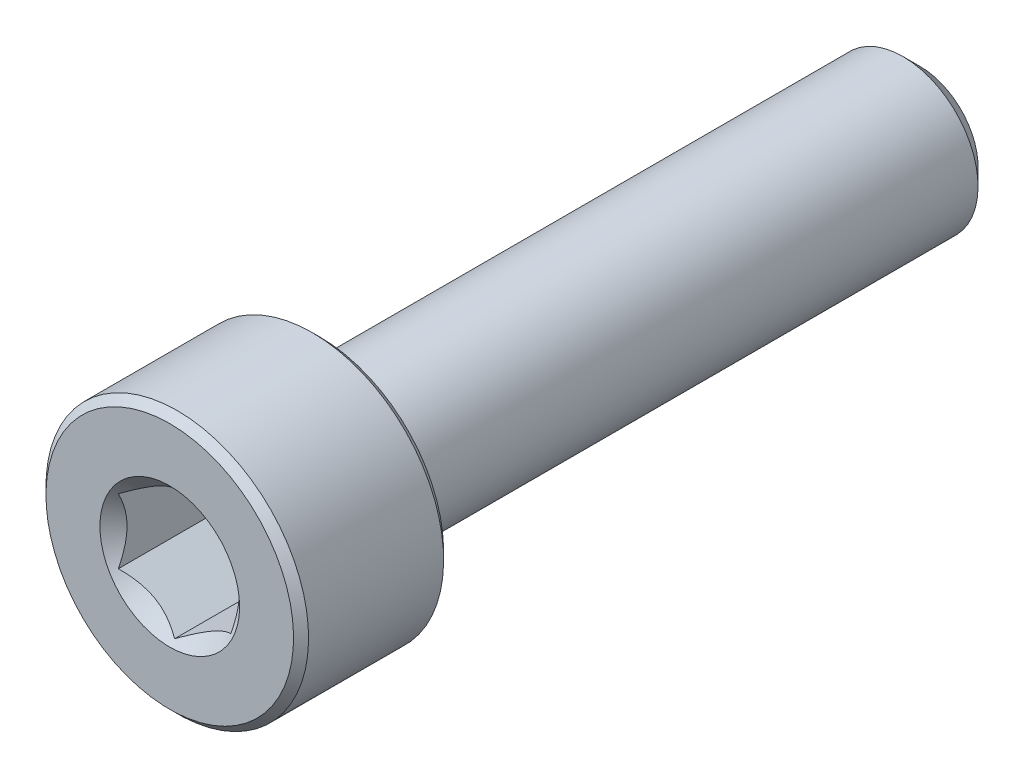
SolidWorks part; units mm, degrees
material "Alloy Steel"
ref_plane "Front Plane" through (0, 0, 0) normal (0, 0, 1) x (1, 0, 0)
ref_plane "Top Plane" through (0, 0, 0) normal (0, 1, 0) x (1, 0, 0)
ref_plane "Right Plane" through (0, 0, 0) normal (1, 0, 0) x (0, 0, -1)
sketch "Sketch1" plane through (0, 0, 0) normal (1, 0, 0) x (0, 0, -1)
  line L0 (-10, 0) -> (10, 0) construction
  line L1 (10, 0) -> (10, 1.5453) construction
  line L2 (10, 1.5453) -> (9.5453, 2) construction
  line L3 (9.5453, 2) -> (9.475, 2) construction
  line L4 (9.475, 2) -> (-6, 2) construction
  line L5 (-6, 2) -> (-6, 3.5) construction
  line L6 (-6, 3.5) -> (-10, 3.5) construction
  line L7 (-10, 3.5) -> (-10, 0) construction
  line L8 (10, 1.5453) -> (10, 2) construction
  line L9 (9.9563, 2.0758) -> (10.3062, 1.4696) construction
  line L10 (10.3062, 1.4696) -> (10.6562, 2.0758) construction
  line L11 (10.6562, 2.0758) -> (9.9563, 2.0758) construction
  line L12 (10.3062, 2.0758) -> (10.3062, 2) construction
  line L13 (10.3062, 1.4696) -> (10.3062, 1.5453) construction
  line L14 (10.2625, 1.5453) -> (10.35, 1.5453) construction
  line L15 (10, 2) -> (10.6125, 2) construction
  line L16 (9.9781, 2.0379) -> (10.6344, 2.0379) construction
  line L17 (10, 0) -> (10, -2) construction
  line L18 (-6.2, 3.5) -> (-6, 3.3) construction
  line L19 (-9.8, 3.5) -> (-10, 3.3) construction
  line L20 (-6, 2) -> (-6, 0) construction
  line L21 (-6, 1) -> (-0.6667, 1) construction
  line L22 (-0.6667, 1) -> (4.6667, 1) construction
  line L23 (4.6667, 1) -> (10, 1) construction
  line L24 (-0.6667, 1) -> (-0.6667, 2) construction
  line L25 (-0.6667, 2) -> (-0.6667, 3.5) construction
  line L26 (4.6667, 1) -> (4.6667, 3.5) construction
  point P0 (-10, 1.5)
  point P3 (8.25, 2)
  point P4 (0, 0)
  point P18 (4.6667, 2)
  point P22 (10.3062, 1.5453)
  point P24 (9.475, 2)
  point P25 (10.3062, 2)
  point P28 (10.3063, 2.0379)
  point P29 (8.25, -2)
  point P30 (-0.6667, 2)
  point P31 (-8, 3.5)
  point P37 (-6.7, 3.5)
  point P38 (-9.7, 3.5)
  point P45 (-0.6667, 1)
  point P46 (4.6667, 1)
  dimension "D2" = 0.0875
  dimension "D7" = 0.2
  dimension "D8" = 0.2
  dimension "D9" = 0.2
  dimension "D10" = 0.1
  dimension "D11" = 0.5
  dimension "Drive Size" = 3
  dimension "Head Diameter" = 7
  dimension "Head Height" = 4
  dimension "Thread Pitch" = 0.7
  dimension "Thread Dia" = 4
  dimension "Length" = 16
  dimension "D12" = 0.525
  dimension "D4" = 1.75
  dimension "D3" = 45
sketch "Sketch2" plane through (0, 0, 0) normal (1, 0, 0) x (0, 0, -1)
  line L0 (-10, 0) -> (-10, 3.3)
  line L1 (-9.8, 3.5) -> (-6.2, 3.5)
  line L2 (-6, 3.3) -> (-6, 2.2)
  line L4 (9.5453, 2) -> (10, 1.5453)
  line L5 (10, 1.5453) -> (10, 0)
  line L6 (-6, 3.5) -> (-10, 3.5) construction
  line L7 (10, 0) -> (-10, 0)
  line L8 (-9.8, 3.5) -> (-10, 3.3) construction
  line L10 (-9.8, 3.5) -> (-10, 3.3)
  line L14 (-6.2, 3.5) -> (-6, 3.3) construction
  line L16 (-6.2, 3.5) -> (-6, 3.3)
  line L17 (-6, 2) -> (-6, 3.5) construction
  line L19 (-5.8, 2) -> (9.5453, 2)
  line L20 (9.475, 2) -> (-6, 2) construction
  arc A1 (-6, 2.2) -> (-5.8, 2) centre (-5.8, 2.2) ccw
  dimension "D3" = 0.2
revolve "Revolve1" add sketch "Sketch2" angle 360 about L7
sketch "Sketch3" plane through (0, 0, 10) normal (0, 0, 1) x (1, 0, 0)
  line L1 (1.5, -0.866) -> (1.5, 0.866)
  line L2 (1.5, 0.866) -> (0, 1.7321)
  line L3 (0, 1.7321) -> (-1.5, 0.866)
  line L4 (-1.5, 0.866) -> (-1.5, -0.866)
  line L5 (-1.5, -0.866) -> (0, -1.7321)
  line L6 (0, -1.7321) -> (1.5, -0.866)
  circle A0 centre (0, 0) radius 1.5 construction
  circle A1 centre (0, 0) radius 3.5 construction
  circle A2 centre (0, 0) radius 3.5 construction
  circle A3 centre (0, 0) radius 1.7321 construction
  point P13 (0, 0)
  dimension "D1" = 3.4641
extrude "Cut-Extrude1" cut sketch "Sketch3" against normal offset from surface (3 mm away) 1 up to face at (0, 3.3, 6)
sketch "Sketch4" plane through (0, 0, 10) normal (0, 0, 1) x (1, 0, 0)
  circle A0 centre (0, 0) radius 1.862
  dimension "D1" = 3.7239
extrude "Cut-Extrude2" cut sketch "Sketch4" against normal up to vertex (2 mm away) draft 45 up to point (0, 3.5, 8)
sketch "Sketch11" plane through (0, 0, 0) normal (1, 0, 0) x (0, 0, -1)
  line L0 (-10, 0) -> (10, 0) construction
  line L1 (-10, 0) -> (10, 0) construction
  line L2 (-3, 0) -> (-3, 2) construction
  line L3 (9.475, 2) -> (-6, 2) construction
  line L4 (7, 0) -> (7, 2) construction
  line L6 (10, 1.5453) -> (10, 2) construction
  point P2 (-3, 0)
  point P3 (7, 0)
  dimension "D2" = 3
sketch "Sketch6" [suppressed] plane through (0, 0, -10) normal (0, 0, -1) x (-1, 0, 0)
  circle A0 centre (0, 0) radius 2
curve "Helix/Spiral1" [suppressed] pitch 0.7 height 16.7 turns 23.8571
sketch "Sketch10" [suppressed] plane through (0, 0, 0) normal (1, 0, 0) x (0, 0, -1)
  line L0 (-5.8, -3.5) -> (-5.8, 3.5)
  line L5 (-10, 0) -> (10, 0) construction
  line L6 (-5.8, 2) -> (-5.8, -2) construction
  point P3 (-5.8, 0)
split "Split1" [suppressed] bodies to split 106
sketch "Sketch7" [suppressed] plane through (0, 0, 0) normal (1, 0, 0) x (0, 0, -1)
  line L0 (9.9781, 2.0379) -> (10.6344, 2.0379)
  line L1 (10.6344, 2.0379) -> (10.35, 1.5453)
  line L2 (10.35, 1.5453) -> (10.2625, 1.5453)
  line L3 (10.2625, 1.5453) -> (9.9781, 2.0379)
sweep "Cut-Sweep1" [suppressed] cut profiles "Sketch7" path "Helix/Spiral1"
sketch "Sketch8" [suppressed] plane through (0, 0, 0) normal (1, 0, 0) x (0, 0, -1)
  line L0 (-6, 0) -> (-6, 2)
  line L1 (-5.8, -2) -> (-5.8, 2) construction
  line L2 (-6, 2) -> (-5.8, 2)
  line L4 (-5.8, 2) -> (-4.6453, 0)
  line L5 (-4.6453, 0) -> (-6, 0)
  line L6 (9.475, 2) -> (-6, 2) construction
  line L7 (-10, 0) -> (10, 0) construction
  dimension "D1" = 60
revolve "Revolve2" [suppressed] add sketch "Sketch8" angle 360 about L5
equation "\"D2@Sketch1\" = \"Thread Pitch@Sketch1\" / 8"
equation "\"D4@Helix/Spiral1\" = \"Thread Pitch@Sketch1\""
equation "\"D7@Sketch1\" = \"Head Height@Sketch1\" * .05"
equation "\"D8@Sketch1\"=\"D7@Sketch1\""
equation "\"D9@Sketch1\"=\"D7@Sketch1\""
equation "\"D10@Sketch1\"=\"D7@Sketch1\"/2"
equation "\"D11@Sketch1\"=\"D10@Sketch1\"*5"
equation "\"D4@Sketch1\"=\"Thread Pitch@Sketch1\"*2.5"
equation "\"D12@Sketch1\"=\"Thread Pitch@Sketch1\"*.75"
equation "\"D3@Helix/Spiral1\"=\"Length@Sketch1\"+\"Thread Pitch@Sketch1\""
equation "\"D3@Sketch2\"=\"Thread Dia@Sketch1\"*0.05"
equation "\"D1@Sketch11\"=\"Length@Sketch1\"*0.1875"
equation "\"D2@Sketch11\"=\"D1@Sketch11\""
equation "\"D1@Sketch4\"=\"D1@Sketch3\"*1.075"
